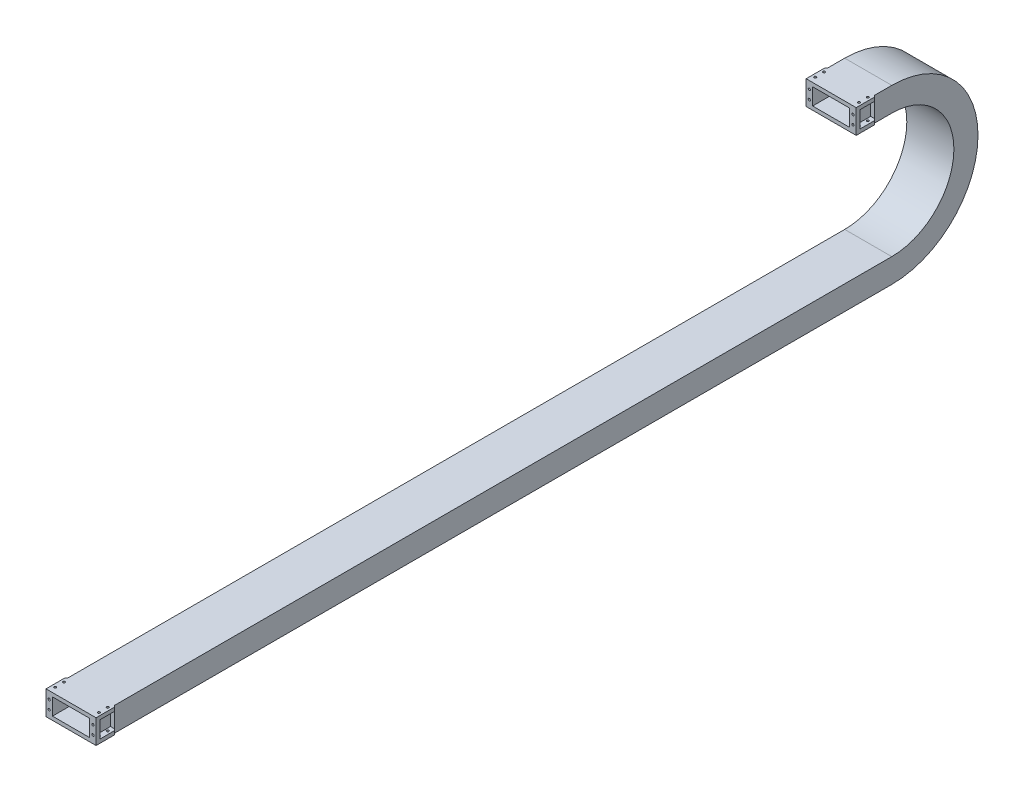
SolidWorks part; units mm, degrees
ref_plane "前基準面" through (0, 0, 0) normal (0, 0, 1) x (1, 0, 0)
ref_plane "上基準面" through (0, 0, 0) normal (0, 1, 0) x (1, 0, 0)
ref_plane "右基準面" through (0, 0, 0) normal (1, 0, 0) x (0, 0, -1)
sketch "草圖1" plane through (0, 0, 0) normal (0, 0, 1) x (1, 0, 0)
  line L0 (-50, -22.5) -> (50, 22.5) construction
  line L1 (-63.5, 32.5) -> (63.5, 32.5)
  line L2 (-63.5, 32.5) -> (-63.5, -32.5)
  line L3 (-63.5, -32.5) -> (63.5, -32.5)
  line L4 (63.5, 32.5) -> (63.5, -32.5)
  line L5 (-50, 22.5) -> (50, 22.5)
  line L6 (-50, 22.5) -> (-50, -22.5)
  line L7 (-50, -22.5) -> (50, -22.5)
  line L8 (50, 22.5) -> (50, -22.5)
  line L9 (-63.5, 32.5) -> (63.5, -32.5) construction
  dimension "D1" = 45
  dimension "D2" = 100
  dimension "D3" = 65
  dimension "D4" = 127
sketch "草圖2" plane through (0, 0, 0) normal (1, 0, 0) x (0, 0, -1)
  line L0 (0, 0) -> (2150, 0)
  line L1 (0, 22.5) -> (0, -22.5) construction
  line L2 (2150, 400) -> (2050, 400)
  arc A0 (2150, 0) -> (2150, 400) centre (2150, 200) ccw
  dimension "D1" = 200
  dimension "D2" = 2150
  dimension "D3" = 100
sweep "掃出1" add profiles "草圖1" path "草圖2"
sketch "草圖5" plane through (63.5, 0, 0) normal (1, 0, 0) x (0, 0, -1)
  line L0 (2150, -32.5) -> (0, -32.5) construction
  line L1 (0, 32.5) -> (50, 32.5)
  line L2 (0, 32.5) -> (0, -32.5)
  line L3 (0, -32.5) -> (50, -32.5)
  line L4 (50, 32.5) -> (50, -32.5)
  line L5 (2150, 367.5) -> (2050, 367.5) construction
  line L6 (2050, 432.5) -> (2100, 432.5)
  line L7 (2050, 432.5) -> (2050, 367.5)
  line L8 (2050, 367.5) -> (2100, 367.5)
  line L9 (2100, 432.5) -> (2100, 367.5)
  dimension "D1" = 50
extrude "伸長1" add sketch "草圖5" along normal blind 4
sketch "草圖6" plane through (-63.5, 0, 0) normal (-1, 0, 0) x (0, 0, 1)
  line L4 (-2050, 432.5) -> (-2100, 432.5)
  line L5 (-2100, 432.5) -> (-2100, 367.5)
  line L6 (-2100, 367.5) -> (-2050, 367.5)
  line L7 (-2050, 367.5) -> (-2050, 432.5)
  line L8 (-2050, 432.5) -> (-2100, 432.5)
  line L9 (-2100, 432.5) -> (-2100, 367.5)
  line L10 (-2100, 367.5) -> (-2050, 367.5)
  line L11 (-2050, 367.5) -> (-2050, 432.5)
  line L12 (0, 32.5) -> (-50, 32.5)
  line L13 (-50, 32.5) -> (-50, -32.5)
  line L14 (-50, -32.5) -> (0, -32.5)
  line L15 (0, -32.5) -> (0, 32.5)
  line L16 (0, 32.5) -> (-50, 32.5)
  line L17 (-50, 32.5) -> (-50, -32.5)
  line L18 (-50, -32.5) -> (0, -32.5)
  line L19 (0, -32.5) -> (0, 32.5)
  dimension "D1" = 0
  dimension "D2" = 0
extrude "伸長2" add sketch "草圖6" along normal blind 4
chamfer "導角1" distance 4 angle 45 12 edges at (63.5, 400, -2100) (65.5, 367.5, -2100) (65.5, 432.5, -2100) (-63.5, 0, -50) (-65.5, 32.5, -50) (-65.5, -32.5, -50)
sketch "草圖9" plane through (67.5, 0, 0) normal (1, 0, 0) x (0, 0, -1)
  line L0 (50, 32.5) -> (0, 32.5) construction
  line L1 (10, 22.5) -> (54, 22.5)
  line L2 (10, 22.5) -> (10, -22.5)
  line L3 (10, -22.5) -> (54, -22.5)
  line L4 (54, 22.5) -> (54, -22.5)
  line L5 (2060, 422.5) -> (2104, 422.5)
  line L6 (2060, 422.5) -> (2060, 377.5)
  line L7 (2060, 377.5) -> (2104, 377.5)
  line L8 (2104, 422.5) -> (2104, 377.5)
  line L9 (0, 32.5) -> (0, -32.5) construction
  line L10 (0, -32.5) -> (50, -32.5) construction
  line L11 (54, 32.5) -> (54, -32.5) construction
  line L12 (2104, 432.5) -> (2104, 367.5) construction
  line L13 (2100, 432.5) -> (2050, 432.5) construction
  line L14 (2050, 432.5) -> (2050, 367.5) construction
  line L15 (2050, 367.5) -> (2100, 367.5) construction
  dimension "D1" = 10
  dimension "D2" = 10
  dimension "D3" = 10
  dimension "D4" = 10
  dimension "D5" = 10
  dimension "D6" = 10
extrude "除料-伸長1" cut sketch "草圖9" against normal blind 15
sketch "草圖10" plane through (-67.5, 0, 0) normal (-1, 0, 0) x (0, 0, 1)
  line L4 (-2060, 422.5) -> (-2104, 422.5)
  line L5 (-2104, 422.5) -> (-2104, 377.5)
  line L6 (-2104, 377.5) -> (-2060, 377.5)
  line L7 (-2060, 377.5) -> (-2060, 422.5)
  line L8 (-2060, 422.5) -> (-2104, 422.5)
  line L9 (-2104, 422.5) -> (-2104, 377.5)
  line L10 (-2104, 377.5) -> (-2060, 377.5)
  line L11 (-2060, 377.5) -> (-2060, 422.5)
  line L12 (-10, 22.5) -> (-54, 22.5)
  line L13 (-54, 22.5) -> (-54, -22.5)
  line L14 (-54, -22.5) -> (-10, -22.5)
  line L15 (-10, -22.5) -> (-10, 22.5)
  line L16 (-10, 22.5) -> (-54, 22.5)
  line L17 (-54, 22.5) -> (-54, -22.5)
  line L18 (-54, -22.5) -> (-10, -22.5)
  line L19 (-10, -22.5) -> (-10, 22.5)
  dimension "D1" = 0
  dimension "D2" = 0
extrude "除料-伸長2" cut sketch "草圖10" against normal blind 15
hole_wizard "Ø6.0 (6) 直徑孔1" positions "草圖4" profile "草圖3" hole size "Ø6.0" standard "ISO"
sketch "草圖4" plane through (0, 32.5, 0) normal (0, 1, 0) x (-1, 0, 0)
  line L0 (0, -27.8753) -> (0, -82.992) construction
  line L2 (-67.5, 0) -> (67.5, 0) construction
  point P0 (59, -40)
  point P1 (59, -16)
  point P3 (-59, -16)
  point P5 (-59, -40)
  dimension "D1" = 16
  dimension "D2" = 24
  dimension "D3" = 118
sketch "草圖3" plane through (-59, 32.5, -40) normal (1, 0, 0) x (0, 0, 1)
  line L0 (0, 0) -> (0, 65)
  line L1 (0, 65) -> (3, 65)
  line L2 (3, 65) -> (3, 0)
  line L5 (3, 0) -> (0, 0)
  line L10 (0, 65) -> (-3, 65) construction
  line L11 (0, -6.35) -> (0, 107.95) construction
  dimension "鑽孔直徑" = 6
  dimension "鑽孔深度" = 65
  dimension "導頭角度" = 180
hole_wizard "Ø6.0 (6) 直徑孔2" positions "草圖8" profile "草圖7" hole size "Ø6.0" standard "ISO"
sketch "草圖8" plane through (0, 432.5, 0) normal (0, 1, 0) x (-1, 0, 0)
  line L0 (0, -2050) -> (0, -1051.3894) construction
  line L1 (67.5, -2050) -> (-67.5, -2050) construction
  point P0 (59, -2090)
  point P1 (59, -2066)
  point P3 (-59, -2090)
  point P5 (-59, -2066)
  dimension "D1" = 118
  dimension "D2" = 16
  dimension "D3" = 24
sketch "草圖7" plane through (-59, 432.5, -2090) normal (1, 0, 0) x (0, 0, 1)
  line L0 (0, 0) -> (0, 65)
  line L1 (0, 65) -> (3, 65)
  line L2 (3, 65) -> (3, 0)
  line L5 (3, 0) -> (0, 0)
  line L10 (0, 65) -> (-3, 65) construction
  line L11 (0, -6.35) -> (0, 107.95) construction
  dimension "鑽孔直徑" = 6
  dimension "鑽孔深度" = 65
  dimension "導頭角度" = 180
hole_wizard "Ø6.0 (6) 直徑孔3" positions "草圖12" profile "草圖11" hole size "Ø6.0" standard "ISO"
sketch "草圖12" plane through (0, 0, 0) normal (0, 0, 1) x (1, 0, 0)
  line L0 (0, 20.3732) -> (0, 0) construction
  line L1 (0, 0) -> (32.8642, 0) construction
  point P0 (-59, 12)
  point P1 (-59, -12)
  point P3 (59, 12)
  point P5 (59, -12)
  dimension "D1" = 24
  dimension "D2" = 118
sketch "草圖11" plane through (-59, 12, 0) normal (1, 0, 0) x (0, -1, 0)
  line L0 (0, 0) -> (0, 10)
  line L1 (0, 10) -> (3, 10)
  line L2 (3, 10) -> (3, 0)
  line L5 (3, 0) -> (0, 0)
  line L11 (0, -6.35) -> (0, 107.95) construction
  dimension "貫穿孔直徑" = 6
  dimension "貫穿孔深度" = 10
hole_wizard "Ø6.0 (6) 直徑孔4" positions "草圖14" profile "草圖13" hole size "Ø6.0" standard "ISO"
sketch "草圖14" plane through (0, 0, -2050) normal (0, 0, 1) x (1, 0, 0)
  line L0 (50, 400) -> (-12.3441, 400) construction
  line L1 (50, 422.5) -> (50, 377.5) construction
  line L3 (0, 422.5) -> (0, 204.8379) construction
  line L4 (-50, 422.5) -> (50, 422.5) construction
  point P0 (-59, 412)
  point P1 (-59, 388)
  point P3 (59, 412)
  point P5 (59, 388)
  dimension "D1" = 24
  dimension "D2" = 118
sketch "草圖13" plane through (-59, 412, -2050) normal (1, 0, 0) x (0, -1, 0)
  line L0 (0, 0) -> (0, 10)
  line L1 (0, 10) -> (3, 10)
  line L2 (3, 10) -> (3, 0)
  line L5 (3, 0) -> (0, 0)
  line L11 (0, -6.35) -> (0, 107.95) construction
  dimension "貫穿孔直徑" = 6
  dimension "貫穿孔深度" = 10
